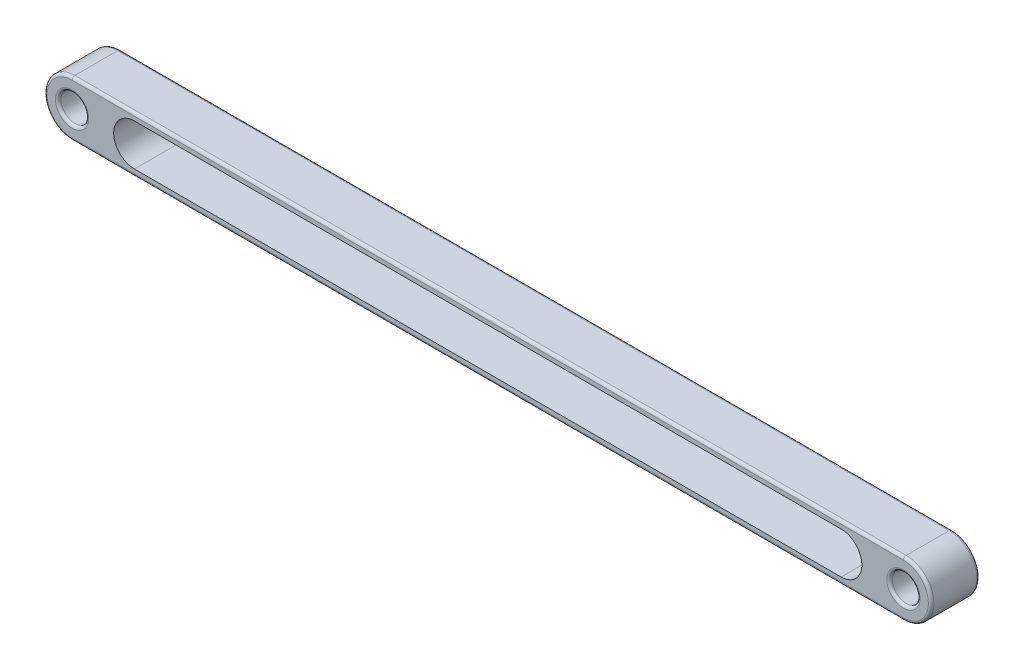
SolidWorks part; units mm, degrees
ref_plane "Front Plane" through (0, 0, 0) normal (0, 0, 1) x (1, 0, 0)
ref_plane "Top Plane" through (0, 0, 0) normal (0, 1, 0) x (1, 0, 0)
ref_plane "Right Plane" through (0, 0, 0) normal (1, 0, 0) x (0, 0, -1)
sketch "Sketch4" plane through (0, 0, 0) normal (0, 0, 1) x (1, 0, 0)
  line L0 (-300, 0) -> (300, 0) construction
  line L1 (-300, 20) -> (300, 20)
  line L2 (-300, -20) -> (300, -20)
  arc A0 (-300, 20) -> (-300, -20) centre (-300, 0) ccw
  arc A1 (300, -20) -> (300, 20) centre (300, 0) ccw
  point P3 (0, 0)
  point P8 (-13.0764, 0)
  point P9 (0, 0)
  dimension "D1" = 640
  dimension "D2" = 40
extrude "Boss-Extrude2" add sketch "Sketch4" along normal mid plane 35
sketch "Sketch5" plane through (0, 0, 17.5) normal (0, 0, 1) x (1, 0, 0)
  circle A0 centre (300, 0) radius 10
  circle A1 centre (-300, 0) radius 10
  dimension "D1" = 20
extrude "Cut-Extrude1" cut sketch "Sketch5" against normal through all
sketch "Sketch6" plane through (0, 0, -17.5) normal (0, 0, -1) x (-1, 0, 0)
  line L0 (-255, 0) -> (255, 0) construction
  line L1 (300, 0) -> (-300, 0) construction
  line L2 (-255, 15) -> (255, 15)
  line L3 (-255, -15) -> (255, -15)
  arc A0 (-255, 15) -> (-255, -15) centre (-255, 0) ccw
  arc A1 (255, -15) -> (255, 15) centre (255, 0) ccw
  point P4 (0, 0)
  point P9 (0, 0)
  point P10 (0, 0)
  point P12 (260.322, 0)
  point P13 (218.1065, 0)
  dimension "D1" = 15
  dimension "D2" = 45
extrude "Cut-Extrude2" cut sketch "Sketch6" against normal blind 40
fillet "Fillet1" radius 2 12 edges at (320, 0, 17.5) (0, -20, 17.5) (-320, 0, 17.5) (320, 0, -17.5) (0, -20, -17.5) (-320, 0, -17.5) (0, 20, 17.5) (0, 20, -17.5) (310, 0, 17.5) (310, 0, -17.5) (-290, 0, 17.5) (-290, 0, -17.5)
